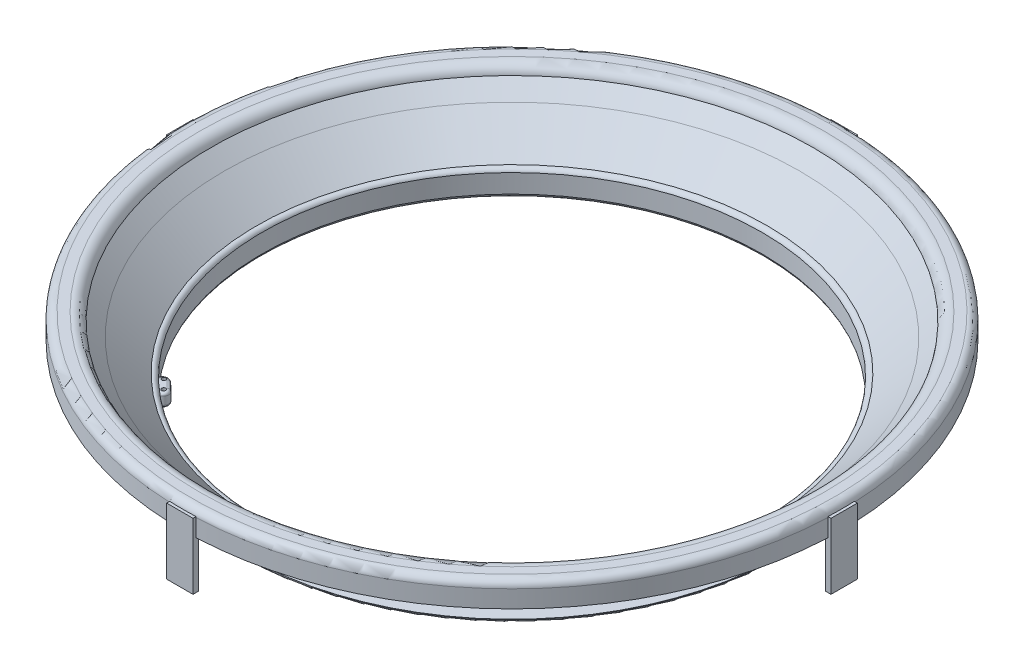
SolidWorks part; units mm, degrees
ref_plane "Front Plane" through (0, 0, 0) normal (0, 0, 1) x (1, 0, 0)
ref_plane "Top Plane" through (0, 0, 0) normal (0, 1, 0) x (1, 0, 0)
ref_plane "Right Plane" through (0, 0, 0) normal (1, 0, 0) x (0, 0, -1)
sketch "Sketch1" plane through (0, 0, 0) normal (0, 0, 1) x (1, 0, 0)
  line L0 (-25.4707, 3.6197) -> (-25.4707, -0.4861) construction
  line L1 (-25.4707, -0.4861) -> (-0.4707, -0.4861) construction
  line L2 (-0.4707, -0.4861) -> (-0.4707, 2.4265) construction
  line L3 (-25.234, 4.3842) -> (-25.234, 4.7257)
  line L15 (-25.234, 3.6197) -> (-25.234, 4.0073)
  line L16 (-24.6623, 5.2624) -> (-24.4932, 5.2624)
  line L17 (-23.4871, 4.6186) -> (-22.4618, 3.5933)
  line L18 (-25.4707, 3.6197) -> (-25.4707, 4.9413)
  line L20 (-21.0658, 2.3008) -> (-19.998, 1.233)
  line L21 (-19.6624, 0.9496) -> (-19.6624, 0.1839)
  line L22 (-19.8487, -0.252) -> (-20.952, -0.252)
  line L25 (-24.8808, 5.4784) -> (-24.1808, 5.4784)
  line L26 (-22.3778, 3.4118) -> (-21.2563, 2.3616)
  line L27 (-23.3203, 4.8345) -> (-22.295, 3.8092)
  line L28 (-22.295, 3.8092) -> (-19.8312, 1.449)
  line L29 (-19.4384, 1.2059) -> (-19.4384, -0.2085)
  line L30 (-19.721, -0.4861) -> (-20.9497, -0.4861)
  line L31 (-25.4707, 3.6197) -> (-25.234, 3.6197)
  line L32 (-20.9497, -0.4861) -> (-20.952, -0.252)
  line L33 (-24.7059, 4.0073) -> (-25.234, 4.0073)
  line L34 (-24.7059, 4.3842) -> (-25.234, 4.3842)
  line L35 (-24.7059, 4.3842) -> (-24.7059, 4.0073)
  line L36 (-24.4932, 4.7083) -> (-24.4932, 5.2624)
  line L37 (-24.1117, 4.7083) -> (-24.1117, 5.2594)
  line L38 (-24.4932, 4.7083) -> (-24.1117, 4.7083)
  arc A1 (-25.234, 4.7257) -> (-24.6623, 5.2624) centre (-24.6798, 4.7083) cw
  arc A2 (-24.1117, 5.2594) -> (-23.4871, 4.6186) centre (-24.2392, 4.5103) cw
  arc A3 (-22.4618, 3.5933) -> (-22.3778, 3.4118) centre (-22.329, 3.5445) ccw
  arc A4 (-21.2563, 2.3616) -> (-21.0658, 2.3008) centre (-21.1306, 2.4265) ccw
  arc A5 (-19.998, 1.233) -> (-19.6624, 0.9496) centre (-19.9719, 0.9235) cw
  arc A6 (-19.6624, 0.1839) -> (-19.8487, -0.252) centre (-19.9735, 0.0591) cw
  arc A9 (-25.4707, 4.9413) -> (-24.8808, 5.4784) centre (-24.9106, 4.9186) cw
  arc A10 (-24.1808, 5.4784) -> (-23.3203, 4.8345) centre (-24.0725, 4.7263) cw
  arc A13 (-19.8312, 1.449) -> (-19.4384, 1.2059) centre (-19.759, 1.1267) cw
  arc A14 (-19.4384, -0.2085) -> (-19.721, -0.4861) centre (-19.815, -0.1078) cw
revolve "Revolve1" add sketch "Sketch1" angle 360 about L2
fillet "Fillet2" radius 0.2 1 edges at (-0.4707, -0.4861, -20.479) type face fillet first side face at (-0.4707, -0.4861, -20.479) second side face at (-0.4707, -0.4861, -19.2503)
sketch "Sketch2" plane through (0, 0, 0) normal (0, 1, 0) x (1, 0, 0)
  line L3 (-13.7216, -13.2616) -> (-13.1417, -13.817) construction
  line L4 (-13.4204, -12.9472) -> (-12.8406, -13.5026)
  line L5 (-14.0227, -13.576) -> (-13.4428, -14.1314)
  arc A3 (-13.4204, -12.9472) -> (-14.0227, -13.576) centre (-13.7216, -13.2616) ccw
  arc A4 (-13.4428, -14.1314) -> (-12.8406, -13.5026) centre (-13.1417, -13.817) ccw
  point P11 (-13.4316, -13.5393)
extrude "Boss-Extrude1" add sketch "Sketch2" along normal blind 1
sketch "Sketch4" plane through (0, 0, 0) normal (0, 1, 0) x (1, 0, 0)
  circle A0 centre (-13.729, -13.1557) radius 0.1532
  circle A1 centre (-13.0561, -13.8379) radius 0.1532
extrude "Cut-Extrude1" cut sketch "Sketch4" along normal blind 1
fillet "Fillet4" radius 0.2 1 edges at (-13.1305, 1, 13.2249) type face fillet first side face at (-13.1305, 0.5, 13.2249) second side face at (-13.0561, 1, 13.9911)
fillet "Fillet5" radius 0.2 1 edges at (-13.1305, 0, 13.2249) type face fillet first side face at (-13.0561, 0, 13.9911) second side face at (-13.1305, 0.4, 13.2249)
sketch "Sketch5" plane through (0, 0, 0) normal (0, 1, 0) x (1, 0, 0)
  line L0 (-0.4707, -25) -> (-0.4707, 25) construction
  line L1 (-25.4707, 0) -> (24.5293, 0) construction
  line L3 (-25.2707, 1) -> (-25.6707, 1)
  line L4 (-25.2707, 1) -> (-25.2707, -1)
  line L5 (-25.2707, -1) -> (-25.6707, -1)
  line L6 (-25.6707, 1) -> (-25.6707, -1)
  line L7 (-25.2707, 1) -> (-25.6707, -1) construction
  line L8 (-25.2707, -1) -> (-25.6707, 1) construction
  line L9 (0.5293, -25.2) -> (-1.4707, -25.2)
  line L10 (0.5293, -25.2) -> (0.5293, -24.8)
  line L11 (0.5293, -24.8) -> (-1.4707, -24.8)
  line L12 (-1.4707, -25.2) -> (-1.4707, -24.8)
  line L13 (0.5293, -25.2) -> (-1.4707, -24.8) construction
  line L14 (0.5293, -24.8) -> (-1.4707, -25.2) construction
  line L15 (24.3293, -1) -> (24.7293, -1)
  line L16 (24.3293, -1) -> (24.3293, 1)
  line L17 (24.3293, 1) -> (24.7293, 1)
  line L18 (24.7293, -1) -> (24.7293, 1)
  line L19 (24.3293, -1) -> (24.7293, 1) construction
  line L20 (24.3293, 1) -> (24.7293, -1) construction
  line L21 (0.5293, 24.8) -> (-1.4707, 24.8)
  line L22 (0.5293, 24.8) -> (0.5293, 25.2)
  line L23 (0.5293, 25.2) -> (-1.4707, 25.2)
  line L24 (-1.4707, 24.8) -> (-1.4707, 25.2)
  line L25 (0.5293, 24.8) -> (-1.4707, 25.2) construction
  line L26 (0.5293, 25.2) -> (-1.4707, 24.8) construction
  circle A2 centre (-0.4707, 0) radius 25 construction
extrude "Boss-Extrude2" add sketch "Sketch5" along normal blind 5
